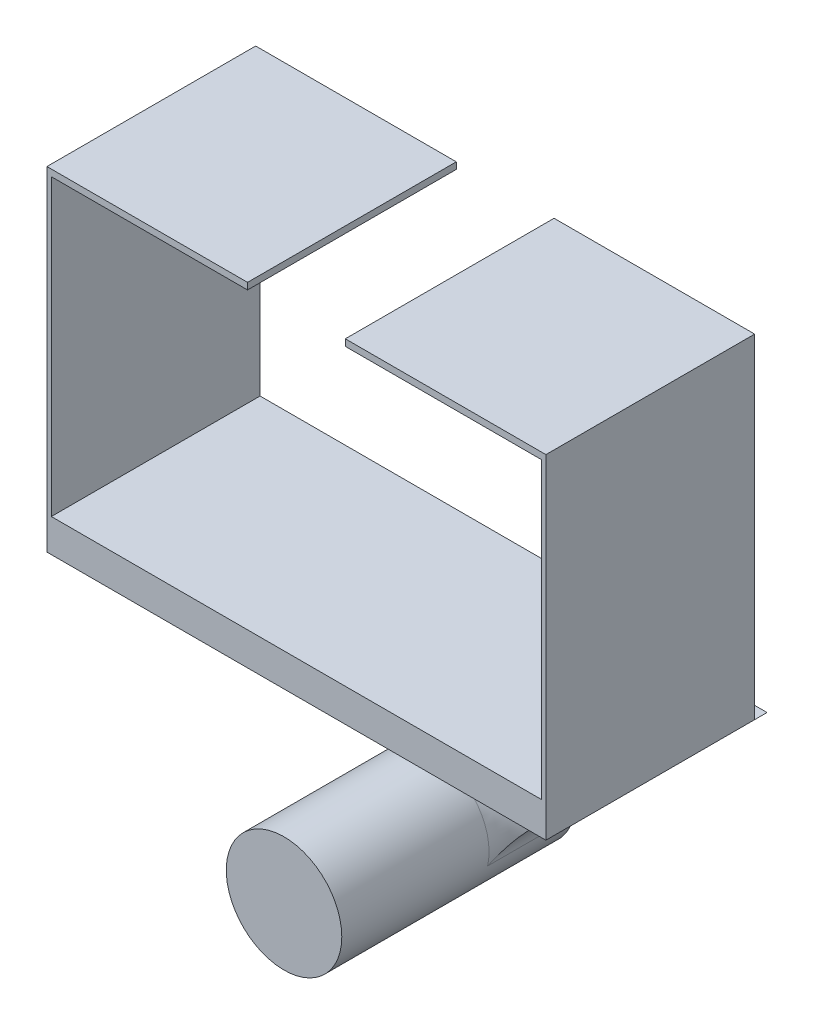
SolidWorks part; units mm, degrees
material "Ti-6Al-4VSolution treated and aged (SS)"
ref_plane "Front Plane" through (0, 0, 0) normal (0, 0, 1) x (1, 0, 0)
ref_plane "Top Plane" through (0, 0, 0) normal (0, 1, 0) x (1, 0, 0)
ref_plane "Right Plane" through (0, 0, 0) normal (1, 0, 0) x (0, 0, -1)
sketch "Sketch1" plane through (0, 0, 0) normal (0, 0, 1) x (1, 0, 0)
  circle A0 centre (0, 0) radius 7.4727
  dimension "D1" = 7.4727
extrude "Boss-Extrude1" add sketch "Sketch1" against normal blind 25.4 contours A0
sketch "Sketch2" plane through (0, 0, -25.4) normal (0, 0, -1) x (-1, 0, 0)
  line L0 (-7.4727, 0) -> (7.4727, 0)
  line L1 (0, 16.0302) -> (0, 9.837) construction
  line L2 (-7.4727, 0) -> (7.4727, 0)
  line L3 (-7.4727, 0) -> (-7.4727, 22.4182)
  line L4 (-7.4727, 22.4182) -> (7.4727, 22.4182)
  line L5 (7.4727, 0) -> (7.4727, 22.4182)
  line L6 (1.5901, 16.0302) -> (1.5901, 9.837)
  line L7 (-1.5901, 16.0302) -> (-1.5901, 9.837)
  circle A0 centre (0, 0) radius 7.4727
  arc A1 (1.5901, 16.0302) -> (-1.5901, 16.0302) centre (0, 16.0302) ccw
  arc A2 (-1.5901, 9.837) -> (1.5901, 9.837) centre (0, 9.837) ccw
  point P5 (0, 0)
  point P8 (0, 12.9336)
  circle M2 centre (0, 0) radius 7.4727
  dimension "D1" = 14.9455
  dimension "D2" = 22.4182
extrude "Boss-Extrude2" add sketch "Sketch2" along normal blind 3.2084 contours L0 M2 | L0 M2 | L3 L2 L5 L4 region at (0, 3.1715, -25.4) region at (0, -3.1715, -25.4)
sketch "Sketch4" plane through (0, 0, -28.6084) normal (0, 0, -1) x (-1, 0, 0)
  line L0 (-7.4727, 22.4182) -> (7.4727, 22.4182) construction
  line L1 (-31.7043, 26.6881) -> (31.7043, 26.6881)
  line L2 (-31.7043, 26.6881) -> (-31.7043, 22.4182)
  line L3 (-31.7043, 22.4182) -> (31.7043, 22.4182)
  line L4 (31.7043, 26.6881) -> (31.7043, 22.4182)
  line L5 (-31.7043, 24.5532) -> (31.7043, 24.5532) construction
  line L6 (0, 24.5532) -> (0, 20.2833)
  line L7 (-7.4727, 0) -> (-8.4475, 0)
  line L8 (-31.7043, 22.4182) -> (-31.7043, 20.2833)
  line L9 (31.7043, 0) -> (7.4727, 0)
  line L10 (-31.7043, 22.4182) -> (-7.4727, 22.4182)
  line L11 (-31.7043, 22.4182) -> (-31.7043, 0)
  line L12 (-31.7043, 0) -> (-7.4727, 0)
  line L13 (-7.4727, 22.4182) -> (-7.4727, 0)
  line L14 (7.4727, 22.4182) -> (7.4727, 0)
  line L15 (31.7043, 22.4182) -> (7.4727, 22.4182)
  line L16 (31.7043, 22.4182) -> (31.7043, 0)
  circle A0 centre (-29.4801, -0.6411) radius 21.0423
  circle A1 centre (29.4801, -0.6411) radius 21.0423
  point P12 (0, 22.4182)
  point P13 (0, 24.5532)
  dimension "D1" = 63.4086
  dimension "D2" = 4.2698
extrude "Boss-Extrude3" add sketch "Sketch4" against normal blind 27.0042 contours L1 L4 L3 L2
sketch "Sketch6" plane through (31.7043, 0, 0) normal (1, 0, 0) x (0, 0, -1)
  line L1 (1.6042, 26.6881) -> (28.6084, 26.6881)
  line L2 (1.6042, 26.6881) -> (1.6042, 22.4182)
  line L3 (1.6042, 22.4182) -> (28.6084, 22.4182)
  line L4 (28.6084, 26.6881) -> (28.6084, 22.4182)
extrude "Boss-Extrude4" add sketch "Sketch6" along normal blind 0.5689
sketch "Sketch7" plane through (0, 26.6881, 0) normal (0, 1, 0) x (1, 0, 0)
  line L0 (31.7043, 1.6042) -> (31.7043, 28.6084) construction
  line L1 (31.7043, 28.6084) -> (32.2732, 28.6084)
  line L2 (31.7043, 28.6084) -> (31.7043, 1.6042)
  line L3 (31.7043, 1.6042) -> (32.2732, 1.6042)
  line L4 (32.2732, 28.6084) -> (32.2732, 1.6042)
  line L5 (32.2732, 28.6084) -> (-31.7043, 28.6084) construction
extrude "Boss-Extrude5" add sketch "Sketch7" along normal blind 38.0746
sketch "Sketch8" plane through (0, 64.7627, 0) normal (0, 1, 0) x (1, 0, 0)
  line L1 (31.7043, 28.6084) -> (32.2732, 28.6084)
  line L2 (31.7043, 28.6084) -> (31.7043, 1.6042)
  line L3 (31.7043, 1.6042) -> (32.2732, 1.6042)
  line L4 (32.2732, 28.6084) -> (32.2732, 1.6042)
extrude "Boss-Extrude6" add sketch "Sketch8" along normal blind 0.8534
sketch "Sketch9" plane through (31.7043, 0, 0) normal (-1, 0, 0) x (0, 0, 1)
  line L0 (-28.6084, 64.7627) -> (-1.6042, 64.7627) construction
  line L1 (-28.6084, 65.6161) -> (-1.6042, 65.6161)
  line L2 (-28.6084, 65.6161) -> (-28.6084, 64.7627)
  line L3 (-28.6084, 64.7627) -> (-1.6042, 64.7627)
  line L4 (-1.6042, 65.6161) -> (-1.6042, 64.7627)
  line L5 (-1.6042, 65.6161) -> (-1.6042, 26.6881) construction
extrude "Boss-Extrude7" add sketch "Sketch9" along normal blind 25.3797
mirror "Mirror1" about plane through (0, 0, 0) normal (1, 0, 0) of "Boss-Extrude7", "Boss-Extrude6", "Boss-Extrude5", "Boss-Extrude4"
sketch "Sketch13" plane through (0, 0, -28.6084) normal (0, 0, -1) x (-1, 0, 0)
  line L0 (0, 22.4182) -> (0, 16.8097)
  line L1 (-32.2732, 22.4182) -> (-7.4727, 22.4182)
  line L2 (-32.2732, 22.4182) -> (-32.2732, 0)
  line L3 (-32.2732, 0) -> (-7.4727, 0)
  line L4 (-7.4727, 22.4182) -> (-7.4727, 0)
  line L5 (32.2732, 0) -> (7.4727, 0)
  line L6 (7.4727, 22.4182) -> (7.4727, 0)
  line L7 (32.2732, 22.4182) -> (7.4727, 22.4182)
  line L8 (32.2732, 22.4182) -> (32.2732, 0)
  line L9 (-7.4727, 0) -> (-32.2732, 22.4182)
  line L10 (7.4727, 0) -> (32.2732, 22.4182)
  line M8 (7.4727, 0) -> (7.4727, 22.4182)
  line M9 (7.4727, 22.4182) -> (32.2732, 22.4182)
  line M21 (-32.2732, 22.4182) -> (-7.4727, 22.4182)
  line M22 (-7.4727, 22.4182) -> (-7.4727, 0)
extrude "Boss-Extrude8" add sketch "Sketch13" against normal blind 3.2084 contours L9 M22 M21 | L10 M8 M9 region at (15.7396, 14.9455, -28.6084) region at (-15.7396, 14.9455, -28.6084)
fillet "Fillet4" radius 6.35 1 edges at (0, 22.4182, -25.4) type face fillet first side face at (0, 22.4182, -13.5021) second side face at (0, 13.0773, -25.4)
fillet "Fillet5" radius 6.35 3 edges at (0, 7.4727, -25.4) (-7.4727, 0, -27.0042) (7.4727, 0, -27.0042) type face fillet first side face at (0, 9.9023, -25.4) first side face at (21.239, 12.444, -25.6764) first side face at (-21.239, 12.444, -25.6764) second side face at (0, 0, -27.0042)
sketch "Sketch14" plane through (0, 0, -28.6084) normal (0, 0, -1) x (-1, 0, 0)
  line L0 (-32.2732, 22.4182) -> (-25.9232, 22.4182)
  line L1 (-25.9232, 22.4182) -> (0, 0)
  line L2 (0, 0) -> (25.9232, 22.4182)
  line L3 (25.9232, 22.4182) -> (32.2732, 22.4182)
  line L17 (9.2013, 1.5625) -> (32.2732, 22.4182)
  line L18 (32.2732, 22.4182) -> (32.2732, 65.6161)
  line L19 (32.2732, 65.6161) -> (6.3246, 65.6161)
  line L20 (6.3246, 65.6161) -> (6.3246, 64.7627)
  line L21 (6.3246, 64.7627) -> (31.7043, 64.7627)
  line L22 (31.7043, 64.7627) -> (31.7043, 26.6881)
  line L23 (31.7043, 26.6881) -> (-31.7043, 26.6881)
  line L24 (-31.7043, 26.6881) -> (-31.7043, 64.7627)
  line L25 (-31.7043, 64.7627) -> (-6.3246, 64.7627)
  line L26 (-6.3246, 64.7627) -> (-6.3246, 65.6161)
  line L27 (-6.3246, 65.6161) -> (-32.2732, 65.6161)
  line L28 (-32.2732, 65.6161) -> (-32.2732, 22.4182)
  line L29 (-32.2732, 22.4182) -> (-9.2013, 1.5625)
  line L30 (9.2013, 1.5625) -> (32.2732, 22.4182)
  line L42 (-32.2732, 22.4182) -> (-9.2013, 1.5625)
  arc A3 (-7.2764, -1.7019) -> (-9.2013, 1.5625) centre (-13.4595, -3.1482) ccw
  arc A4 (-7.2764, -1.7019) -> (7.2764, -1.7019) centre (0, 0) ccw
  arc A5 (9.2013, 1.5625) -> (7.2764, -1.7019) centre (13.4595, -3.1482) ccw
  arc A6 (-7.2764, -1.7019) -> (-9.2013, 1.5625) centre (-13.4595, -3.1482) ccw
  arc A7 (-7.2764, -1.7019) -> (7.2764, -1.7019) centre (0, 0) ccw
  arc A8 (9.2013, 1.5625) -> (7.2764, -1.7019) centre (13.4595, -3.1482) ccw
  dimension "D1" = 6.35
  dimension "D2" = 6.35
  dimension "D3" = 0
extrude "Boss-Extrude9" add sketch "Sketch14" along normal blind 1.6042
equation "\"a\"= 0.498"
equation "\"b\"= 0.9992"
equation "\"c\"= 1.499"
equation "\"sf\"= 4"
equation "\"F\"= 600"
equation "\"E\"= 15199999.87"
equation "\"delt_max\"= 0.005"
equation "\"stress_y\"= 120000"
equation "\"L1\"= 1"
equation "\"W\"= 2 * \"F\""
equation "\"stress\"= \"stress_y\" / \"sf\""
equation "\"delt\"= \"delt_max\" / \"sf\""
equation "\"A1\"= \"F\" / \"stress\""
equation "\"Z\"= \"W\" / ( 2 * \"stress\" )"
equation "\"r1\"= ( ( 4 * \"Z\" ) / PI ) ^ ( 1 / 3 )"
equation "\"w1\"= 2 * \"r1\""
equation "\"t1\"= \"A1\" / \"w1\""
equation "\"base1\"= \"t1\" + \"L1\""
equation "\"h1\"= ( \"A1\" * 2 ) / \"base1\""
equation "\"w2\"= \"A1\" / \"c\""
equation "\"h2\"= \"A1\" / \"b\""
equation "\"I1\"= ( 5 * \"W\" * ( \"L1\" ^ 3 ) ) / ( 384 * \"E\" * \"delt\" )"
equation "\"r2\"= ( ( \"I1\" * 4 ) / PI ) ^ ( 1 / 4 )"
equation "\"L2\"= 4 * \"r2\""
equation "\"w3\"= 2 * \"r2\""
equation "\"A2\"= ( \"F\" * \"L2\" ) / ( \"E\" * \"delt\" )' "
equation "\"t2\"= \"A2\" / \"w3\"' "
equation "\"base2\"= \"L1\" + \"t2\""
equation "\"L3\"= \"a\" + ( 2 * \"b\" )' "
equation "\"I2\"= ( 5 * \"W\" * ( \"base2\" ^ 3 ) ) / ( 384 * \"E\" * \"delt\" )"
equation "\"h3\"= ( ( 12 * \"I2\" ) / \"L3\" ) ^ ( 1 / 3 )"
equation "\"A3\"= ( \"F\" * \"base2\" ) / ( \"E\" * \"delt\" )"
equation "\"w4\"= \"A3\" / \"c\""
equation "\"h4\"= \"A3\" / \"b\""
equation "\"D1@Sketch1\"=\"r1\""
equation "\"D1@Boss-Extrude1\"=\"L1\""
equation "\"D1@Sketch2\"=\"r1\"*2"
equation "\"D2@Sketch2\"=3*\"r1\""
equation "\"D1@Sketch4\"=\"L3\""
equation "\"D2@Sketch4\"=\"h3\""
equation "\"D1@Boss-Extrude3\"=\"base2\""
equation "\"D1@Boss-Extrude4\"=\"w4\""
equation "\"D1@Boss-Extrude5\"=\"c\""
equation "\"D1@Boss-Extrude6\"=\"h4\""
equation "\"D1@Boss-Extrude7\"=\"b\""
equation "\"D1@Boss-Extrude2\"=\"t2\" * 2"
equation "\"dss\"= \"t1\""
equation "\"D1@Boss-Extrude8\"=\"t2\" * 2"
equation "\"D1@Boss-Extrude9\"= \"t2\""
